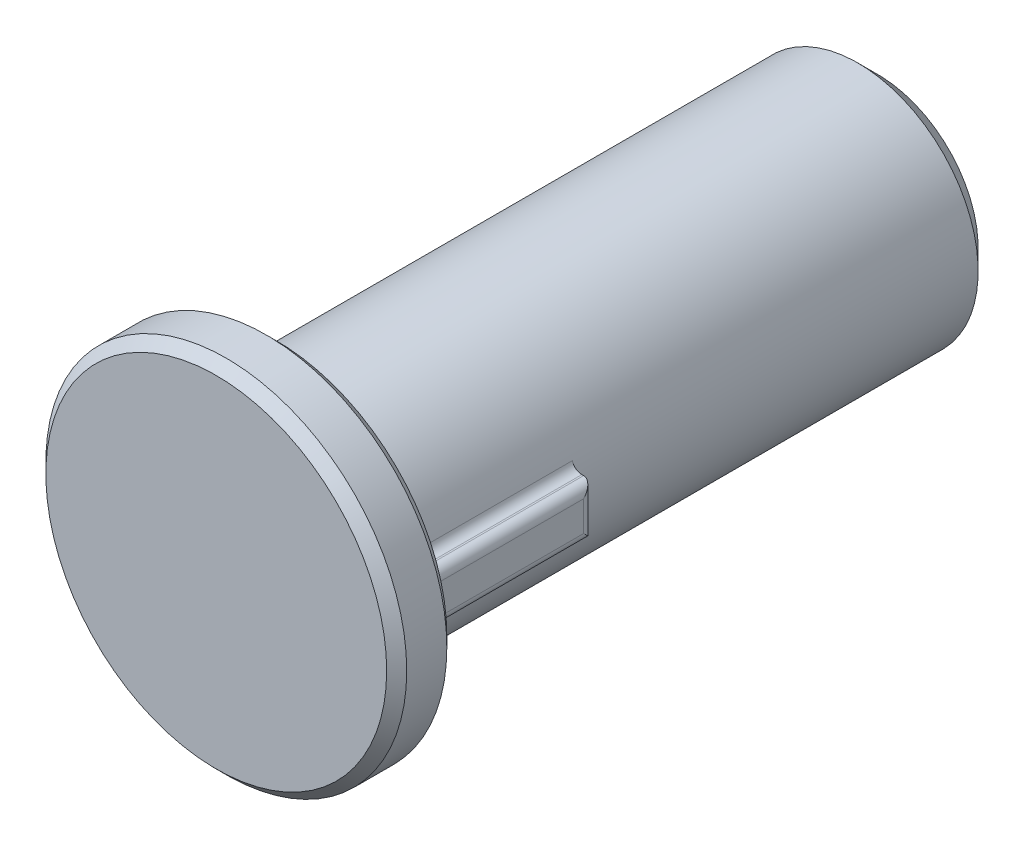
SolidWorks part; units mm, degrees
ref_plane "Front" through (0, 0, 0) normal (0, 0, 1) x (1, 0, 0)
ref_plane "Top" through (0, 0, 0) normal (0, 1, 0) x (1, 0, 0)
ref_plane "Right" through (0, 0, 0) normal (1, 0, 0) x (0, 0, -1)
other "Configuration Table"
sketch "Sketch1" plane through (0, 0, 0) normal (0, 0, 1) x (1, 0, 0)
  circle A0 centre (0, 0) radius 9
extrude "Boss-Extrude1" add sketch "Sketch1" along normal blind 3
sketch "Sketch2" plane through (0, 0, 0) normal (0, 0, -1) x (-1, 0, 0)
  circle A0 centre (0, 0) radius 6
  circle A1 centre (0, 0) radius 9 construction
extrude "Boss-Extrude2" add sketch "Sketch2" along normal blind 30
sketch "Sketch3" plane through (0, 0, 0) normal (0, 0, -1) x (-1, 0, 0)
  line L1 (-5.1745, 1.3372) -> (-6.8242, 1.3372)
  line L2 (-5.1745, 1.3372) -> (-5.1745, -1.1628)
  line L3 (-5.1745, -1.1628) -> (-6.8242, -1.1628)
  line L4 (-6.8242, 1.3372) -> (-6.8242, -1.1628)
  line L5 (-5.1745, 1.3372) -> (-6.8242, -1.1628) construction
  line L6 (-5.1745, -1.1628) -> (-6.8242, 1.3372) construction
  circle A0 centre (0, 0) radius 6 construction
  point P0 (-5.9994, 0.0872)
  point P5 (-5.9987, -0.1254)
  dimension "D1" = 2.5
extrude "Boss-Extrude3" add sketch "Sketch3" along normal blind 9
fillet "Fillet1" radius 0.5 5 edges at (6.8242, 0.0872, -9) (6.8242, -1.1628, -4.5) (6.8242, 1.3372, -4.5) (5.8862, -1.1628, -4.5) (5.8491, 1.3372, -4.5)
chamfer "Chamfer1" distance 0.5 angle 45 10 edges at (9, 0, 3) (9, 0, 0) (6.8242, 0.0872, 0) (6.6778, -1.0164, 0) (6.6778, 1.1907, 0) (6.304, -1.1628, 0) (6.2796, 1.3372, 0) (5.9787, -1.2666, 0) (5.9355, 1.4368, 0) (-5.9994, -0.0836, 0)
chamfer "Chamfer2" distance 1 angle 45 1 edges at (-6, 0, -30)
sketch "Sketch4" plane through (0, 0, -30) normal (0, 0, -1) x (-1, 0, 0)
  line L0 (-1.9223, -2.3032) -> (2.5025, -1.6545)
  arc A0 (2.5025, -1.6545) -> (-1.9223, -2.3032) centre (0, 0) ccw
  circle A1 centre (0, 0) radius 5 construction
  dimension "D1" = 2
extrude "Cut-Extrude1" cut sketch "Sketch4" against normal blind 10
chamfer "Chamfer3" distance 0.5 angle 45 2 edges at (0.4352, 2.9683, -30) (-0.2901, -1.9788, -30)
